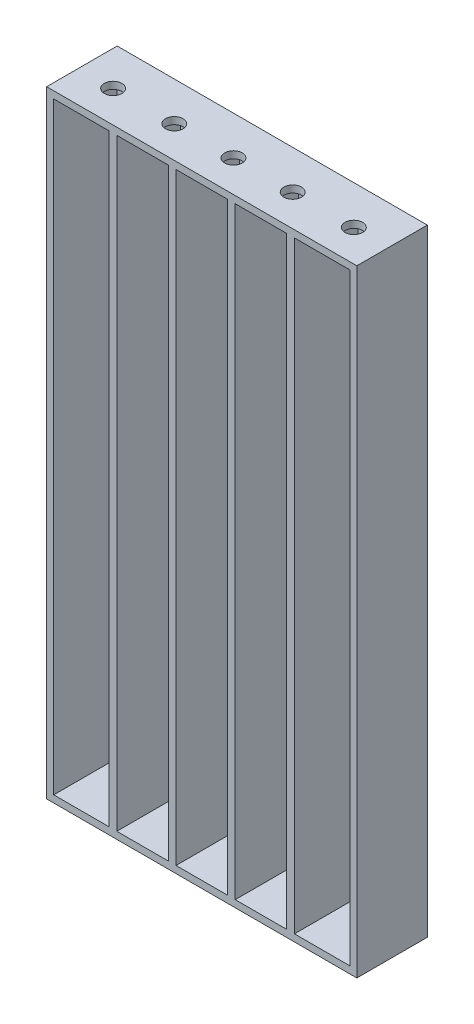
SolidWorks part; units mm, degrees
ref_plane "Front Plane" through (0, 0, 0) normal (0, 0, 1) x (1, 0, 0)
ref_plane "Top Plane" through (0, 0, 0) normal (0, 1, 0) x (1, 0, 0)
ref_plane "Right Plane" through (0, 0, 0) normal (1, 0, 0) x (0, 0, -1)
sketch "Sketch1" plane through (0, 0, 0) normal (0, 0, 1) x (1, 0, 0)
  line L1 (-44, -87.5) -> (44, -87.5)
  line L2 (-44, -87.5) -> (-44, 87.5)
  line L3 (-44, 87.5) -> (44, 87.5)
  line L4 (44, -87.5) -> (44, 87.5)
  line L5 (-44, -87.5) -> (44, 87.5) construction
  line L6 (-44, 87.5) -> (44, -87.5) construction
  point P0 (0, 0)
  dimension "D1" = 88
  dimension "D2" = 175
extrude "Boss-Extrude1" add sketch "Sketch1" along normal blind 2
sketch "Sketch2" plane through (0, 0, 2) normal (0, 0, 1) x (1, 0, 0)
  line L4 (44, -87.5) -> (44, 87.5)
  line L5 (44, 87.5) -> (-44, 87.5)
  line L6 (-44, 87.5) -> (-44, -87.5)
  line L7 (-44, -87.5) -> (44, -87.5)
  line L8 (44, -87.5) -> (44, 87.5)
  line L9 (44, 87.5) -> (-44, 87.5)
  line L10 (-44, 87.5) -> (-44, -87.5)
  line L11 (-44, -87.5) -> (44, -87.5)
  dimension "D1" = 0
extrude "Extrude-Thin1" add sketch "Sketch2" along normal blind 18 thin thin type one direction reverse wall 2
sketch "Sketch3" plane through (0, 0, 2) normal (0, 0, 1) x (1, 0, 0)
  line L0 (-25.2, 85.5) -> (-25.2, -85.5)
  line L1 (42, 85.5) -> (-42, 85.5) construction
  line L2 (-42, -85.5) -> (42, -85.5) construction
  line L3 (-8.4, 85.5) -> (-8.4, -85.5)
  line L4 (42, 85.5) -> (-42, 85.5) construction
  line L5 (25.2, 85.5) -> (25.2, -85.5)
  line L6 (8.4, 85.5) -> (8.4, -85.5)
  line L7 (-42, -85.5) -> (42, -85.5) construction
  line L8 (-42, 85.5) -> (-42, -85.5) construction
  line L9 (42, -85.5) -> (42, 85.5) construction
  dimension "D1" = 16.8
  dimension "D2" = 16.8
  dimension "D3" = 16.8
  dimension "D4" = 16.8
  dimension "D5" = 16.8
extrude "Extrude-Thin2" add sketch "Sketch3" along normal blind 18 thin thin type mid plane wall 2.2
sketch "Sketch4" plane through (0, 87.5, 0) normal (0, 1, 0) x (1, 0, 0)
  line L0 (26.3, -20) -> (26.3, -2) construction
  line L1 (26.3, -2) -> (42, -2) construction
  line L2 (42, -2) -> (42, -20) construction
  line L3 (42, -20) -> (26.3, -20) construction
  line L4 (9.5, -20) -> (9.5, -2) construction
  line L5 (9.5, -2) -> (24.1, -2) construction
  line L6 (24.1, -2) -> (24.1, -20) construction
  line L7 (24.1, -20) -> (9.5, -20) construction
  line L8 (-7.3, -2) -> (7.3, -2) construction
  line L9 (7.3, -2) -> (7.3, -20) construction
  line L10 (7.3, -20) -> (-7.3, -20) construction
  line L11 (-7.3, -20) -> (-7.3, -2) construction
  line L12 (-24.1, -2) -> (-9.5, -2) construction
  line L13 (-9.5, -2) -> (-9.5, -20) construction
  line L14 (-9.5, -20) -> (-24.1, -20) construction
  line L15 (-24.1, -20) -> (-24.1, -2) construction
  line L16 (-42, -2) -> (-26.3, -2) construction
  line L17 (-26.3, -2) -> (-26.3, -20) construction
  line L18 (-26.3, -20) -> (-42, -20) construction
  line L19 (-42, -20) -> (-42, -2) construction
  line L20 (26.3, -20) -> (26.3, -2) construction
  line L21 (26.3, -2) -> (42, -2) construction
  line L22 (42, -2) -> (42, -20) construction
  line L23 (42, -20) -> (26.3, -20) construction
  line L24 (9.5, -20) -> (9.5, -2) construction
  line L25 (9.5, -2) -> (24.1, -2) construction
  line L26 (24.1, -2) -> (24.1, -20) construction
  line L27 (24.1, -20) -> (9.5, -20) construction
  line L28 (-7.3, -2) -> (7.3, -2) construction
  line L29 (7.3, -2) -> (7.3, -20) construction
  line L30 (7.3, -20) -> (-7.3, -20) construction
  line L31 (-7.3, -20) -> (-7.3, -2) construction
  line L32 (-24.1, -2) -> (-9.5, -2) construction
  line L33 (-9.5, -2) -> (-9.5, -20) construction
  line L34 (-9.5, -20) -> (-24.1, -20) construction
  line L35 (-24.1, -20) -> (-24.1, -2) construction
  line L36 (-42, -2) -> (-26.3, -2) construction
  line L37 (-26.3, -2) -> (-26.3, -20) construction
  line L38 (-26.3, -20) -> (-42, -20) construction
  line L39 (-42, -20) -> (-42, -2) construction
  line L40 (42, -11) -> (-42, -11) construction
  line L41 (-16.8, -20) -> (-16.8, -2) construction
  line L42 (-34.15, -20) -> (-34.15, -2) construction
  line L43 (0, -20) -> (0, -2) construction
  line L44 (16.8, -20) -> (16.8, -2) construction
  line L45 (34.15, -20) -> (34.15, -2) construction
  point P26 (34.15, -11)
  point P28 (16.8, -11)
  point P30 (0, -11)
  point P31 (-16.8, -11)
  point P34 (-34.15, -11)
hole_wizard "Ø5.0mm Dowel Hole3" positions "Sketch5" profile "Sketch6" hole size "Ø5.0" standard "BSI" end condition up to next
sketch "Sketch5" plane through (0, 87.5, 0) normal (0, 1, 0) x (1, 0, 0)
  line L0 (-34.15, -20) -> (-34.15, -2) construction
  line L1 (-16.8, -20) -> (-16.8, -2) construction
  point P0 (-34.15, -11)
  point P4 (-16.8, -11)
  point P8 (0, -11)
  point P11 (16.8, -11)
  point P14 (34.15, -11)
sketch "Sketch6" plane through (-34.15, 87.5, 11) normal (1, 0, 0) x (0, 0, 1)
  line L0 (0, 0) -> (0, 2)
  line L1 (0, 2) -> (2.5, 2)
  line L2 (2.5, 2) -> (2.5, 0)
  line L5 (2.5, 0) -> (0, 0)
  line L11 (0, -6.35) -> (0, 107.95) construction
  dimension "Thru Hole Dia." = 5
  dimension "Thru Hole Depth" = 2
